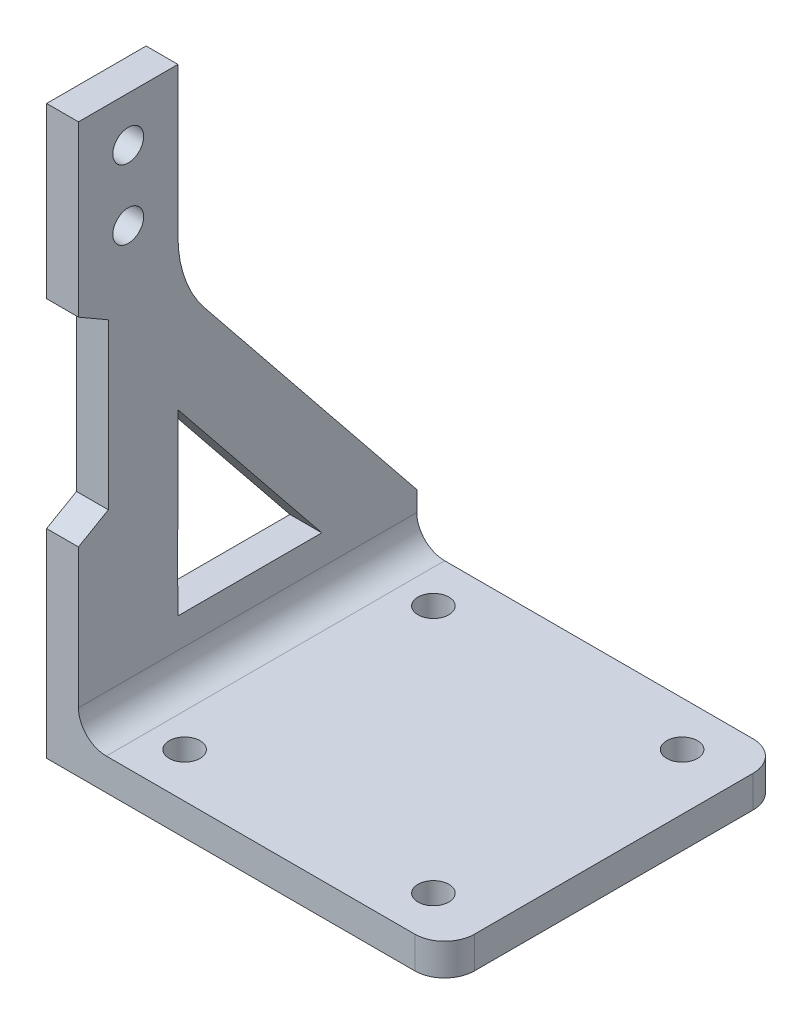
SolidWorks part; units mm, degrees
ref_plane "Front Plane" through (0, 0, 0) normal (0, 0, 1) x (1, 0, 0)
ref_plane "Top Plane" through (0, 0, 0) normal (0, 1, 0) x (1, 0, 0)
ref_plane "Right Plane" through (0, 0, 0) normal (1, 0, 0) x (0, 0, -1)
sketch "Sketch1" plane through (0, 0, 0) normal (0, 0, 1) x (1, 0, 0)
  line L0 (0, 0) -> (0, 57)
  line L1 (0, 0) -> (40, 0)
  line L2 (3.2, 3.2) -> (40, 3.2)
  line L3 (3.2, 3.2) -> (3.2, 57)
  line L4 (0, 57) -> (3.2, 57)
  line L5 (40, 0) -> (40, 3.2)
  dimension "D1" = 57
  dimension "D2" = 40
  dimension "D3" = 3.2
extrude "Boss-Extrude1" add sketch "Sketch1" along normal blind 17 and the other way blind 17
fillet "Fillet1" radius 2.8 1 edges at (3.2, 3.2, 0)
sketch "Sketch4" plane through (0, 0, 0) normal (0, -1, 0) x (1, 0, 0)
  line L0 (40, -17) -> (40, 17) construction
  line L1 (0, -17) -> (40, -17) construction
  circle A4 centre (9.37, -12.5) radius 1.5
  circle A5 centre (9.37, 12.5) radius 1.5
  circle A6 centre (34.37, -12.5) radius 1.5
  circle A7 centre (34.37, 12.5) radius 1.5
  dimension "D1" = 25
  dimension "D2" = 25
  dimension "D4" = 5.63
  dimension "D5" = 25
  dimension "D6" = 4.5
extrude "Cut-Extrude2" cut sketch "Sketch4" against normal blind 20
sketch "Sketch5" plane through (0, 0, 0) normal (0, -1, 0) x (1, 0, 0)
  circle A0 centre (9.37, 12.5) radius 1.55
  circle A1 centre (34.37, 12.5) radius 1.55
  circle A2 centre (9.37, -12.5) radius 1.55
  circle A3 centre (34.37, -12.5) radius 1.55
  dimension "D1" = 3.1
extrude "Cut-Extrude3" cut sketch "Sketch5" against normal up to next
sketch "Sketch6" plane through (0, 0, 0) normal (-1, 0, 0) x (0, 0, 1)
  line L0 (7, 57) -> (-17, 57)
  line L3 (-17, 57) -> (-17, 8)
  line L6 (0, 0) -> (0, 54.6269) construction
  line L7 (7, 37.8) -> (-17, 8)
  line L8 (7, 57) -> (7, 37.8)
extrude "Cut-Extrude4" cut sketch "Sketch6" against normal blind 4 and the other way through all
fillet "Fillet3" radius 3 2 edges at (40, 1.6, -17) (40, 1.6, 17)
sketch "Sketch7" plane through (0, 0, 0) normal (-1, 0, 0) x (0, 0, 1)
  line L0 (-7.4547, 9) -> (7, 9)
  line L1 (0, 0) -> (0, 34.1612) construction
  line L2 (7.0285, 12.4099) -> (7, 9)
  line L3 (7.0047, 26.9538) -> (-7.4547, 9)
  line L5 (7.0047, 26.9538) -> (7.0285, 12.4099)
extrude "Cut-Extrude5" cut sketch "Sketch7" against normal blind 5
sketch "Sketch8" plane through (0, 0, 0) normal (-1, 0, 0) x (0, 0, 1)
  line L0 (12, 57) -> (12, 43.92) construction
  line L1 (7, 57) -> (17, 57) construction
  line L2 (7, 57) -> (17, 57) construction
  circle A4 centre (12, 52.47) radius 1.55
  circle A5 centre (12, 45.47) radius 1.55
  dimension "D2" = 4.53
  dimension "D3" = 3.1
  dimension "D4" = 3.1
  dimension "D1" = 7
extrude "Cut-Extrude8" cut sketch "Sketch8" against normal blind 10
sketch "Croquis1" plane through (0, 0, 0) normal (-1, 0, 0) x (0, 0, 1)
  line L0 (17, 20) -> (14, 21.7321)
  line L1 (17, 57) -> (17, 0) construction
  line L2 (14, 21.7321) -> (14, 38.2679)
  line L3 (14, 38.2679) -> (17, 40)
  line L4 (17, 20) -> (17, 40)
  line L5 (7, 57) -> (17, 57) construction
  dimension "D1" = 120
  dimension "D2" = 120
  dimension "D3" = 3
  dimension "D4" = 20
  dimension "D5" = 17
extrude "Cortar-Extruir1" cut sketch "Croquis1" against normal up to next contours L0 L2 L3 L4
fillet "Redondeo1" radius 12 1 edges at (1.6, 37.8, 7)
